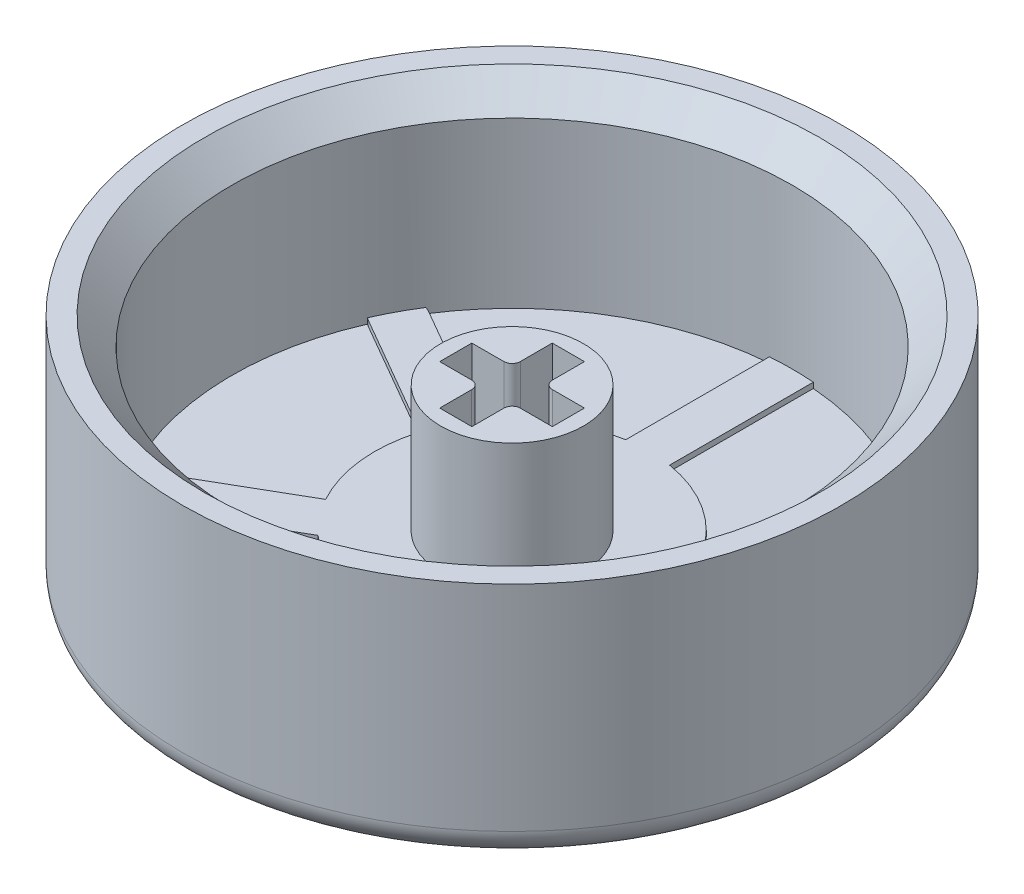
SolidWorks part; units mm, degrees
ref_plane "Front Plane" through (0, 0, 0) normal (0, 0, 1) x (1, 0, 0)
ref_plane "Top Plane" through (0, 0, 0) normal (0, 1, 0) x (1, 0, 0)
ref_plane "Right Plane" through (0, 0, 0) normal (1, 0, 0) x (0, 0, -1)
sketch "Sketch1" plane through (0, 0, 0) normal (0, 1, 0) x (1, 0, 0)
  circle A0 centre (0, 0) radius 12
  dimension "D1" = 24
extrude "button top" add sketch "Sketch1" along normal blind 1.8
sketch "Sketch2" plane through (0, 1.8, 0) normal (0, 1, 0) x (1, 0, 0)
  circle A3 centre (0, 0) radius 12
  circle A4 centre (0, 0) radius 12 construction
  circle A5 centre (0, 0) radius 10.2
  dimension "D1" = 1.8
extrude "button walls" add sketch "Sketch2" along normal blind 7
sketch "Sketch5" plane through (0, 1.8, 0) normal (0, 1, 0) x (1, 0, 0)
  circle A0 centre (0, 0) radius 5
  dimension "D1" = 10
extrude "offset" add sketch "Sketch5" along normal blind 0.2
sketch "Sketch3" plane through (0, 1.8, 0) normal (0, 1, 0) x (1, 0, 0)
  line L0 (0, -2.05) -> (0, 2.05) construction
  line L1 (-2.05, 0) -> (2.05, 0) construction
  line L2 (-0.585, 0.885) -> (-0.585, 2.05)
  line L3 (-0.585, -2.05) -> (0.585, -2.05)
  line L4 (-0.585, -2.05) -> (-0.585, -0.885)
  line L5 (-0.585, 2.05) -> (0.585, 2.05)
  line L6 (0.585, -2.05) -> (0.585, -0.885)
  line L7 (-0.585, -2.05) -> (0.585, 2.05) construction
  line L8 (-0.585, 2.05) -> (0.585, -2.05) construction
  line L9 (-2.05, -0.585) -> (-0.885, -0.585)
  line L10 (-2.05, -0.585) -> (-2.05, 0.585)
  line L11 (-2.05, 0.585) -> (-0.885, 0.585)
  line L12 (2.05, -0.585) -> (2.05, 0.585)
  line L13 (-2.05, -0.585) -> (2.05, 0.585) construction
  line L14 (-2.05, 0.585) -> (2.05, -0.585) construction
  line L15 (0.885, 0.585) -> (2.05, 0.585)
  line L16 (0.585, 0.885) -> (0.585, 2.05)
  line L17 (0.885, -0.585) -> (2.05, -0.585)
  circle A0 centre (0, 0) radius 2.6
  arc A1 (-0.585, -0.885) -> (-0.885, -0.585) centre (-0.885, -0.885) ccw
  arc A2 (0.585, -0.885) -> (0.885, -0.585) centre (0.885, -0.885) cw
  arc A3 (0.885, 0.585) -> (0.585, 0.885) centre (0.885, 0.885) cw
  arc A4 (-0.585, 0.885) -> (-0.885, 0.585) centre (-0.885, 0.885) cw
  point P6 (0, 0)
  point P9 (0, 0)
  point P22 (2.05, 0)
  point P24 (0, 2.05)
  point P29 (0.585, -0.585)
  point P32 (0.585, 0.585)
  dimension "D1" = 5.2
  dimension "D4" = 0.3
  dimension "D2" = 4.1
  dimension "D3" = 1.17
extrude "stem housing" add sketch "Sketch3" along normal blind 4.6 from surface starting at face at (0, 2, 5)
sketch "Sketch4" plane through (0, 1.8, 0) normal (0, 1, 0) x (1, 0, 0)
  line L0 (0, 2.6) -> (0, 10.2) construction
  line L1 (-0.8, 2.6) -> (-0.8, 10.2)
  line L2 (0.8, 2.6) -> (0.8, 10.2)
  line L3 (2.5981, 1.5) -> (9.1799, 5.3) construction
  line L4 (2.1981, 2.1928) -> (8.7799, 5.9928)
  line L5 (2.9981, 0.8072) -> (9.5799, 4.6072)
  line L6 (2.9445, -1.3) -> (9.5263, -5.1) construction
  line L7 (3.3445, -0.6072) -> (9.9263, -4.4072)
  line L8 (2.5445, -1.9928) -> (9.1263, -5.7928)
  line L9 (0.6928, -3) -> (0.6928, -10.6) construction
  line L10 (1.4928, -3) -> (1.4928, -10.6)
  line L11 (-0.1072, -3) -> (-0.1072, -10.6)
  line L12 (-1.9053, -1.9) -> (-8.487, -5.7) construction
  line L13 (-1.5053, -2.5928) -> (-8.087, -6.3928)
  line L14 (-2.3053, -1.2072) -> (-8.887, -5.0072)
  line L15 (-2.2517, 0.9) -> (-8.8335, 4.7) construction
  line L16 (-2.6517, 0.2072) -> (-9.2335, 4.0072)
  line L17 (-1.8517, 1.5928) -> (-8.4335, 5.3928)
  circle A0 centre (0, 0) radius 2.6 construction
  circle A1 centre (0, 0) radius 2.6 construction
  circle A2 centre (0, 0) radius 10.2 construction
  arc A3 (-0.8, 2.6) -> (0.8, 2.6) centre (0, 2.6) ccw
  arc A4 (0.8, 10.2) -> (-0.8, 10.2) centre (0, 10.2) ccw
  arc A5 (2.1981, 2.1928) -> (2.9981, 0.8072) centre (2.5981, 1.5) ccw
  arc A6 (9.5799, 4.6072) -> (8.7799, 5.9928) centre (9.1799, 5.3) ccw
  arc A7 (3.3445, -0.6072) -> (2.5445, -1.9928) centre (2.9445, -1.3) ccw
  arc A8 (9.1263, -5.7928) -> (9.9263, -4.4072) centre (9.5263, -5.1) ccw
  arc A9 (1.4928, -3) -> (-0.1072, -3) centre (0.6928, -3) ccw
  arc A10 (-0.1072, -10.6) -> (1.4928, -10.6) centre (0.6928, -10.6) ccw
  arc A11 (-1.5053, -2.5928) -> (-2.3053, -1.2072) centre (-1.9053, -1.9) ccw
  arc A12 (-8.887, -5.0072) -> (-8.087, -6.3928) centre (-8.487, -5.7) ccw
  arc A13 (-2.6517, 0.2072) -> (-1.8517, 1.5928) centre (-2.2517, 0.9) ccw
  arc A14 (-8.4335, 5.3928) -> (-9.2335, 4.0072) centre (-8.8335, 4.7) ccw
  point P9 (0, 6.4)
  point P18 (5.889, 3.4)
  point P25 (6.2354, -3.2)
  point P32 (0.6928, -6.8)
  point P39 (-5.1962, -3.8)
  point P46 (-5.5426, 2.8)
  point P51 (0.3464, -0.2)
  dimension "D1" = 1.6
  dimension "D2" = 6
extrude "spokes" add sketch "Sketch4" along normal up to surface (0.2 mm away) up to face at (0, 2, 5)
fillet "Fillet1" radius 1 1 edges at (0, 0, 12)
chamfer "Chamfer1" distance 1 angle 45 1 edges at (0, 8.8, 10.2)
